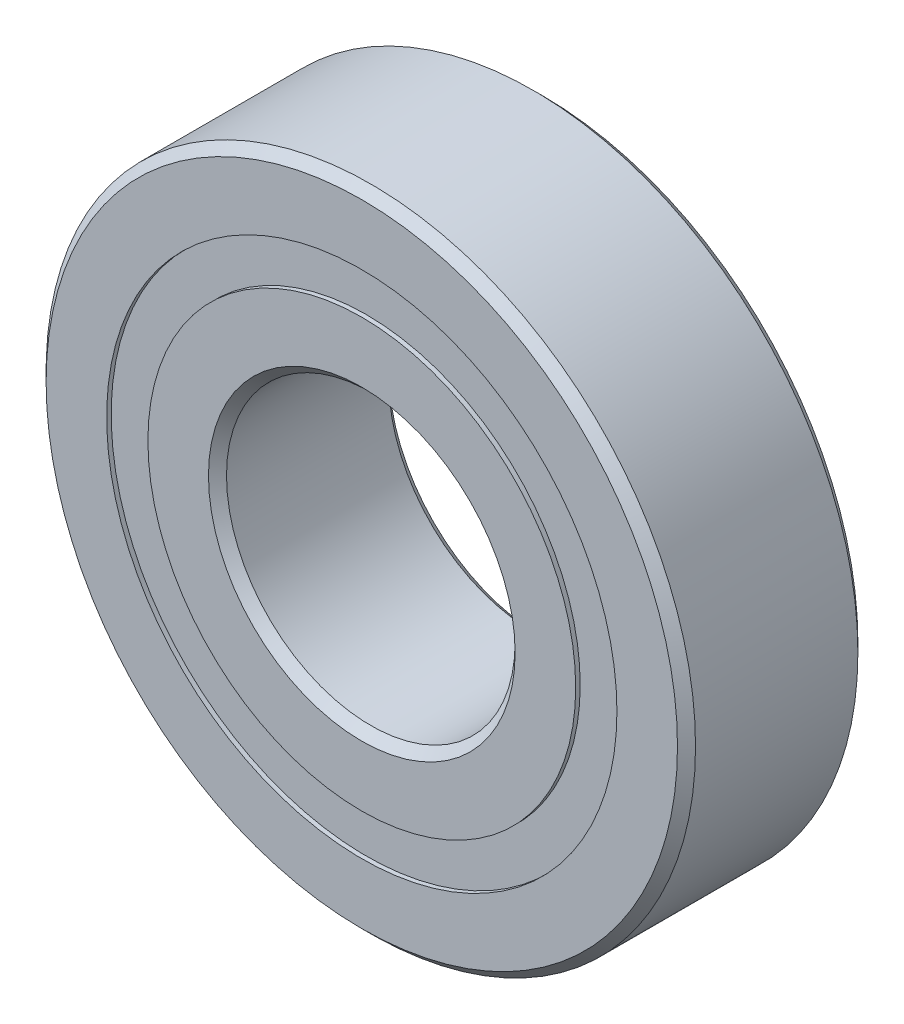
SolidWorks part; units mm, degrees
ref_plane "Front Plane" through (0, 0, 0) normal (0, 0, 1) x (1, 0, 0)
ref_plane "Top Plane" through (0, 0, 0) normal (0, 1, 0) x (1, 0, 0)
ref_plane "Right Plane" through (0, 0, 0) normal (1, 0, 0) x (0, 0, -1)
sketch "Sketch1" plane through (0, 0, 0) normal (1, 0, 0) x (0, 0, -1)
  line L0 (-3.9688, 0) -> (3.9688, 0) construction
  line L1 (0, 14.2875) -> (0, -14.2875) construction
  line L2 (3.5719, 14.2875) -> (-3.5719, 14.2875)
  line L3 (-3.5719, 14.2875) -> (-3.9688, 13.8906)
  line L4 (-3.9688, 13.8906) -> (-3.9688, 11.2259)
  line L5 (-3.9688, 11.2259) -> (-1.7639, 11.2259)
  line L6 (3.9688, 11.2259) -> (1.7639, 11.2259)
  line L7 (3.9688, 13.8906) -> (3.9688, 11.2259)
  line L8 (3.5719, 14.2875) -> (3.9688, 13.8906)
  line L9 (0, 14.2875) -> (0, 10.3187) construction
  line L10 (0, 10.3187) -> (0, 6.35) construction
  arc A0 (-1.7639, 11.2259) -> (1.7639, 11.2259) centre (0, 10.3187) cw
  point P14 (0, 6.35)
  dimension "Width" = 7.9375
  dimension "OD" = 28.575
  dimension "D1" = 45
  dimension "D2" = 0.3969
  dimension "Shaft Dia" = 12.7
  dimension "D3" = 3.5278
  dimension "D4" = 0.9071
revolve "Revolve1" add sketch "Sketch1" angle 360 about L0
sketch "Sketch3" plane through (0, 0, 0) normal (1, 0, 0) x (0, 0, -1)
  line L0 (-3.9687, 9.4116) -> (-1.7639, 9.4116)
  line L1 (0, 14.2875) -> (0, -14.2875) construction
  line L2 (-3.9688, 13.8906) -> (-3.9688, 11.2259) construction
  line L3 (-3.9687, 9.4116) -> (-3.9688, 6.7469)
  line L4 (-3.5719, 14.2875) -> (-3.9688, 13.8906) construction
  line L5 (-3.9688, 6.7469) -> (-3.5719, 6.35)
  line L6 (-3.5719, 6.35) -> (3.5719, 6.35)
  line L7 (3.5719, 14.2875) -> (3.5719, -14.2875) construction
  line L8 (3.5719, 6.35) -> (3.9688, 6.7469)
  line L9 (3.9688, -13.8906) -> (3.9688, 13.8906) construction
  line L10 (3.9688, 6.7469) -> (3.9687, 9.4116)
  line L11 (3.9687, 9.4116) -> (1.7639, 9.4116)
  line L13 (3.5719, 14.2875) -> (3.9688, 13.8906) construction
  arc A0 (1.7639, 11.2259) -> (-1.7639, 11.2259) centre (0, 10.3187) ccw construction
  arc A1 (1.7639, 9.4116) -> (-1.7639, 9.4116) centre (0, 10.3187) cw
revolve "Revolve3" add sketch "Sketch3" angle 360 about L0
sketch "Sketch4" plane through (0, 0, 0) normal (1, 0, 0) x (0, 0, -1)
  line L0 (-1.9835, 10.3187) -> (1.9835, 10.3187)
  arc A2 (-1.9835, 10.3187) -> (1.9835, 10.3187) centre (0, 10.3187) cw
  arc A3 (1.7639, 11.2259) -> (-1.7639, 11.2259) centre (0, 10.3187) ccw construction
revolve "Revolve4" add sketch "Sketch4" angle 360 about L0
ref_axis "Axis1" through (0, 0, -3.9688) along (0, 0, 1)
pattern_circular "CirPattern1" count 10 every 36 about axis through (0, 0, -3.9688) along (0, 0, 1) of bodies 104
sketch "Sketch5" plane through (0, 0, 0) normal (1, 0, 0) x (0, 0, -1)
  line L0 (-3.9688, 11.2259) -> (-1.7639, 11.2259) construction
  line L1 (-3.7703, 11.2259) -> (-1.9835, 11.2259)
  line L2 (-3.7703, 11.2259) -> (-3.7703, 9.4116)
  line L3 (-3.7703, 9.4116) -> (-1.9835, 9.4116)
  line L4 (-1.9835, 11.2259) -> (-1.9835, 9.4116)
  line L5 (-3.9687, 9.4116) -> (-1.7639, 9.4116) construction
  line L6 (3.9688, 11.2259) -> (1.7639, 11.2259) construction
  line L7 (3.7703, 11.2259) -> (1.9835, 11.2259)
  line L8 (3.7703, 11.2259) -> (3.7703, 9.4116)
  line L9 (3.7703, 9.4116) -> (1.9835, 9.4116)
  line L10 (1.9835, 11.2259) -> (1.9835, 9.4116)
  line L11 (3.9687, 9.4116) -> (1.7639, 9.4116) construction
  line L12 (-3.5719, 14.2875) -> (-3.9688, 13.8906) construction
  point P18 (-3.7703, 14.0891)
revolve "Revolve5" add sketch "Sketch5" angle 360 about L0
equation "\"D2@Sketch1\" = \"Width@Sketch1\"*.05"
equation "\"D3@Sketch1\" = \"Width@Sketch1\"/2.25"
equation "\"D4@Sketch1\" = (((\"OD@Sketch1\"-\"Width@Sketch1\")/2)/3.25)/3.5"
equation "\"D2@CirPattern1\" = 360/\"Balls@CirPattern1\""
